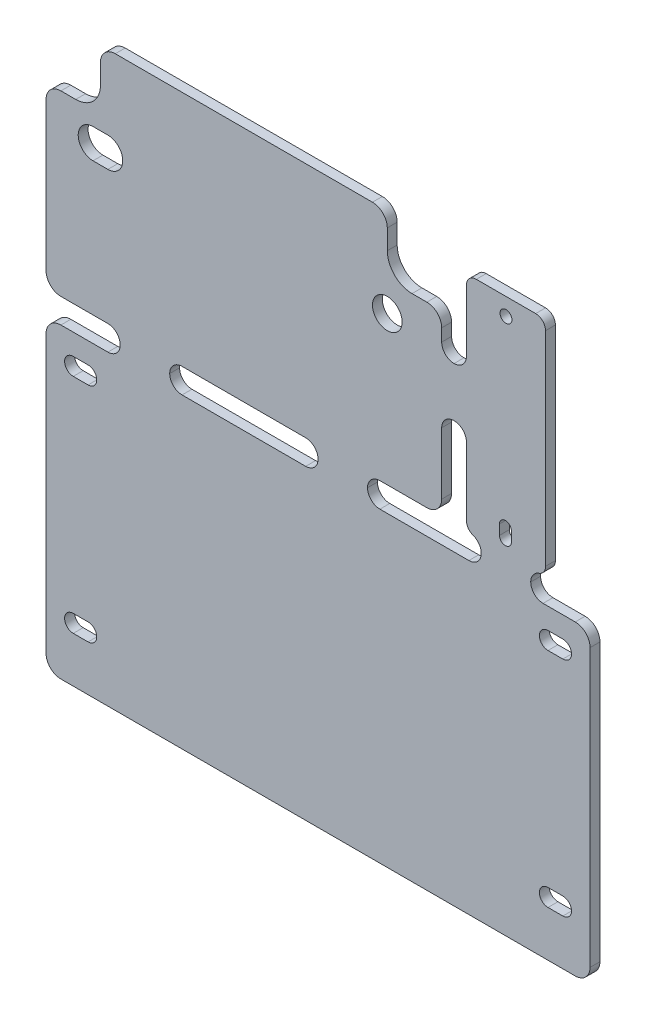
SolidWorks part; units mm, degrees
ref_plane "正面" through (0, 0, 0) normal (0, 0, 1) x (1, 0, 0)
ref_plane "平面" through (0, 0, 0) normal (0, 1, 0) x (1, 0, 0)
ref_plane "右側面" through (0, 0, 0) normal (1, 0, 0) x (0, 0, -1)
sketch "ｽｹｯﾁ1" plane through (0, 0, 0) normal (0, 0, 1) x (1, 0, 0)
  line L0 (-49.5, 24.75) -> (-46.5, 24.75)
  line L1 (55, 32.5) -> (-55, 32.5)
  line L2 (55, 32.5) -> (55, -32.5)
  line L3 (55, -32.5) -> (-55, -32.5)
  line L4 (-55, 32.5) -> (-55, -32.5)
  line L5 (55, 32.5) -> (-55, -32.5) construction
  line L6 (55, -32.5) -> (-55, 32.5) construction
  line L7 (-46.5, 28.25) -> (-49.5, 28.25)
  line L8 (-46.5, 28.25) -> (-46.5, 24.75) construction
  line L10 (-49.5, 28.25) -> (-49.5, 24.75) construction
  line L11 (-46.5, 28.25) -> (-49.5, 24.75) construction
  line L12 (-46.5, 24.75) -> (-49.5, 28.25) construction
  line L13 (-55, 4) -> (55, 4) construction
  line L14 (0, 32.5) -> (0, -32.5) construction
  line L15 (-46.5, -20.25) -> (-49.5, -20.25)
  line L16 (-49.5, -16.75) -> (-46.5, -16.75)
  line L17 (46.5, -20.25) -> (49.5, -20.25)
  line L18 (49.5, -16.75) -> (46.5, -16.75)
  line L19 (46.5, 28.25) -> (49.5, 28.25)
  line L20 (49.5, 24.75) -> (46.5, 24.75)
  arc A2 (-49.5, 28.25) -> (-49.5, 24.75) centre (-49.5, 26.5) ccw
  arc A3 (-46.5, 28.25) -> (-46.5, 24.75) centre (-46.5, 26.5) cw
  arc A4 (-49.5, -20.25) -> (-49.5, -16.75) centre (-49.5, -18.5) cw
  arc A5 (-46.5, -20.25) -> (-46.5, -16.75) centre (-46.5, -18.5) ccw
  arc A6 (46.5, -20.25) -> (46.5, -16.75) centre (46.5, -18.5) cw
  arc A7 (49.5, -20.25) -> (49.5, -16.75) centre (49.5, -18.5) ccw
  arc A8 (49.5, 28.25) -> (49.5, 24.75) centre (49.5, 26.5) cw
  arc A9 (46.5, 28.25) -> (46.5, 24.75) centre (46.5, 26.5) ccw
  point P0 (0, 0)
  point P6 (-48, 26.5)
  dimension "D3" = 3.5
  dimension "D4" = 3
  dimension "D1" = 65
  dimension "D2" = 110
  dimension "D5" = 6
  dimension "D6" = 7
  dimension "D7" = 22.5
extrude "ﾎﾞｽ - 押し出し1" add sketch "ｽｹｯﾁ1" along normal blind 2
fillet "ﾌｨﾚｯﾄ1" radius 3 2 edges at (55, 32.5, 1) (-55, 32.5, 1)
sketch "ｽｹｯﾁ2" plane through (0, 0, 2) normal (0, 0, 1) x (1, 0, 0)
  line L0 (-45.5, 64.5) -> (-42.5, 64.5)
  line L2 (-55, 85.5) -> (-55, 37.5) construction
  line L3 (-55, 37.5) -> (25, 37.5) construction
  line L4 (25, 85.5) -> (25, 37.5) construction
  line L5 (-55, 85.5) -> (25, 37.5) construction
  line L6 (-55, 37.5) -> (25, 85.5) construction
  line L7 (-45.5, 70.5) -> (-42.5, 70.5)
  line L8 (-45.5, 70.5) -> (-45.5, 64.5) construction
  line L10 (-42.5, 70.5) -> (-42.5, 64.5) construction
  line L11 (-45.5, 70.5) -> (-42.5, 64.5) construction
  line L12 (-45.5, 64.5) -> (-42.5, 70.5) construction
  line L17 (-44, 67.5) -> (14, 67.5) construction
  line L18 (-15, 85.5) -> (-15, 37.5) construction
  line L24 (-55, 85.5) -> (25, 85.5) construction
  line L25 (-55, 37.5) -> (25, 37.5)
  line L26 (25, 37.5) -> (25, 73.5)
  line L27 (25, 73.5) -> (14, 73.5)
  line L28 (14, 73.5) -> (14, 85.5)
  line L29 (14, 85.5) -> (-44, 85.5)
  line L30 (-44, 73.5) -> (-44, 85.5)
  line L31 (-55, 73.5) -> (-44, 73.5)
  line L32 (-55, 37.5) -> (-55, 73.5)
  line L33 (-55, 29.5) -> (-55, -32.5) construction
  line L34 (52, 32.5) -> (-52, 32.5) construction
  arc A0 (-45.5, 70.5) -> (-45.5, 64.5) centre (-45.5, 67.5) ccw
  arc A1 (-42.5, 70.5) -> (-42.5, 64.5) centre (-42.5, 67.5) cw
  circle A2 centre (14, 67.5) radius 3
  point P0 (-15, 61.5)
  point P5 (-44, 67.5)
  dimension "D6" = 6
  dimension "D7" = 29
  dimension "D1" = 80
  dimension "D2" = 48
  dimension "D3" = 6
  dimension "D4" = 3
  dimension "D5" = 29
  dimension "D8" = 12
  dimension "D9" = 11
  dimension "D10" = 18
  dimension "D11" = 5
extrude "ﾎﾞｽ - 押し出し2" add sketch "ｽｹｯﾁ2" against normal blind 2 separate body
fillet "ﾌｨﾚｯﾄ5" radius 3 6 edges at (-44, 85.5, 1) (-55, 73.5, 1) (14, 85.5, 1) (25, 73.5, 1) (25, 37.5, 1) (-55, 37.5, 1)
fillet "ﾌｨﾚｯﾄ6" radius 5 2 edges at (14, 73.5, 1) (-44, 73.5, 1)
sketch "ｽｹｯﾁ4" plane through (0, 0, 2) normal (0, 0, 1) x (1, 0, 0)
  line L0 (-40, 37.5) -> (-40, 32.5)
  line L1 (-52, 37.5) -> (22, 37.5) construction
  line L2 (52, 32.5) -> (-52, 32.5) construction
  line L3 (-40, 32.5) -> (-30, 32.5)
  line L4 (-30, 32.5) -> (-30, 37.5)
  line L5 (-30, 37.5) -> (-40, 37.5)
  line L6 (0, 37.5) -> (0, 32.5)
  line L7 (0, 32.5) -> (10, 32.5)
  line L8 (10, 32.5) -> (10, 37.5)
  line L9 (10, 37.5) -> (0, 37.5)
  line L10 (-55, 70.5) -> (-55, 40.5) construction
  line L11 (25, 40.5) -> (25, 70.5) construction
  dimension "D1" = 10
  dimension "D2" = 10
  dimension "D3" = 15
  dimension "D4" = 15
extrude "ﾎﾞｽ - 押し出し4" add sketch "ｽｹｯﾁ4" against normal blind 2
fillet "ﾌｨﾚｯﾄ7" radius 2.5 8 edges at (10, 37.5, 1) (10, 32.5, 1) (0, 37.5, 1) (0, 32.5, 1) (-30, 37.5, 1) (-30, 32.5, 1) (-40, 37.5, 1) (-40, 32.5, 1)
sketch "ｽｹｯﾁ5" plane through (0, 0, 2) normal (0, 0, 1) x (1, 0, 0)
  line L0 (36.6832, 42) -> (36.6832, 40)
  line L1 (30, 82.5) -> (46, 82.5)
  line L2 (30, 82.5) -> (30, 37.5)
  line L3 (30, 37.5) -> (46, 37.5)
  line L4 (46, 82.5) -> (46, 37.5)
  line L5 (30, 82.5) -> (46, 37.5) construction
  line L6 (30, 37.5) -> (46, 82.5) construction
  line L7 (39.0832, 42) -> (36.6832, 42) construction
  line L8 (39.0832, 42) -> (39.0832, 40)
  line L9 (39.0832, 40) -> (36.6832, 40) construction
  line L11 (39.0832, 42) -> (36.6832, 40) construction
  line L12 (39.0832, 40) -> (36.6832, 42) construction
  line L13 (25, 40.5) -> (25, 70.5) construction
  line L14 (52, 32.5) -> (12.5, 32.5) construction
  circle A0 centre (38, 79) radius 1.2
  arc A1 (36.6832, 42) -> (39.0832, 42) centre (37.8832, 42) cw
  arc A2 (39.0832, 40) -> (36.6832, 40) centre (37.8832, 40) cw
  point P0 (38, 60)
  point P7 (37.8832, 41)
  dimension "D3" = 2.4
  dimension "D1" = 45
  dimension "D2" = 16
  dimension "D4" = 2.4
  dimension "D5" = 2
  dimension "D6" = 19
  dimension "D7" = 19
  dimension "D8" = 5
  dimension "D9" = 5
extrude "ﾎﾞｽ - 押し出し5" add sketch "ｽｹｯﾁ5" against normal blind 2 separate body
sketch "ｽｹｯﾁ6" plane through (0, 0, 2) normal (0, 0, 1) x (1, 0, 0)
  line L0 (33, 37.5) -> (33, 32.5)
  line L1 (30, 37.5) -> (46, 37.5) construction
  line L2 (52, 32.5) -> (12.5, 32.5) construction
  line L3 (33, 32.5) -> (43, 32.5)
  line L4 (43, 32.5) -> (43, 37.5)
  line L5 (43, 37.5) -> (33, 37.5)
  line L6 (25, 65.5) -> (30, 65.5)
  line L7 (25, 40.5) -> (25, 70.5) construction
  line L8 (30, 82.5) -> (30, 37.5) construction
  line L9 (30, 65.5) -> (30, 55.5)
  line L10 (30, 55.5) -> (25, 55.5)
  line L11 (25, 55.5) -> (25, 65.5)
  line L13 (12.5, 37.5) -> (22, 37.5) construction
  dimension "D1" = 10
  dimension "D2" = 10
  dimension "D3" = 3
  dimension "D4" = 18
extrude "ﾎﾞｽ - 押し出し6" add sketch "ｽｹｯﾁ6" against normal blind 2
fillet "ﾌｨﾚｯﾄ8" radius 2.5 8 edges at (43, 32.5, 1) (43, 37.5, 1) (33, 32.5, 1) (33, 37.5, 1) (30, 55.5, 1) (25, 55.5, 1) (25, 65.5, 1) (30, 65.5, 1)
fillet "ﾌｨﾚｯﾄ9" radius 2 4 edges at (46, 82.5, 1) (30, 82.5, 1) (46, 37.5, 1) (30, 37.5, 1)
sketch "ｽｹｯﾁ7" plane through (0, 0, 2) normal (0, 0, 1) x (1, 0, 0)
  line L0 (-55, -32.5) -> (55, -32.5)
  line L1 (55, -32.5) -> (55, -29.5)
  line L2 (55, -32.5) -> (55, 29.5) construction
  line L3 (55, -29.5) -> (-55, -29.5)
  line L4 (-55, 29.5) -> (-55, -32.5) construction
  line L5 (-55, -29.5) -> (-55, -32.5)
  dimension "D1" = 3
extrude "ｶｯﾄ - 押し出し1" cut sketch "ｽｹｯﾁ7" against normal blind 10
fillet "ﾌｨﾚｯﾄ10" radius 3 2 edges at (55, -29.5, 1) (-55, -29.5, 1)
